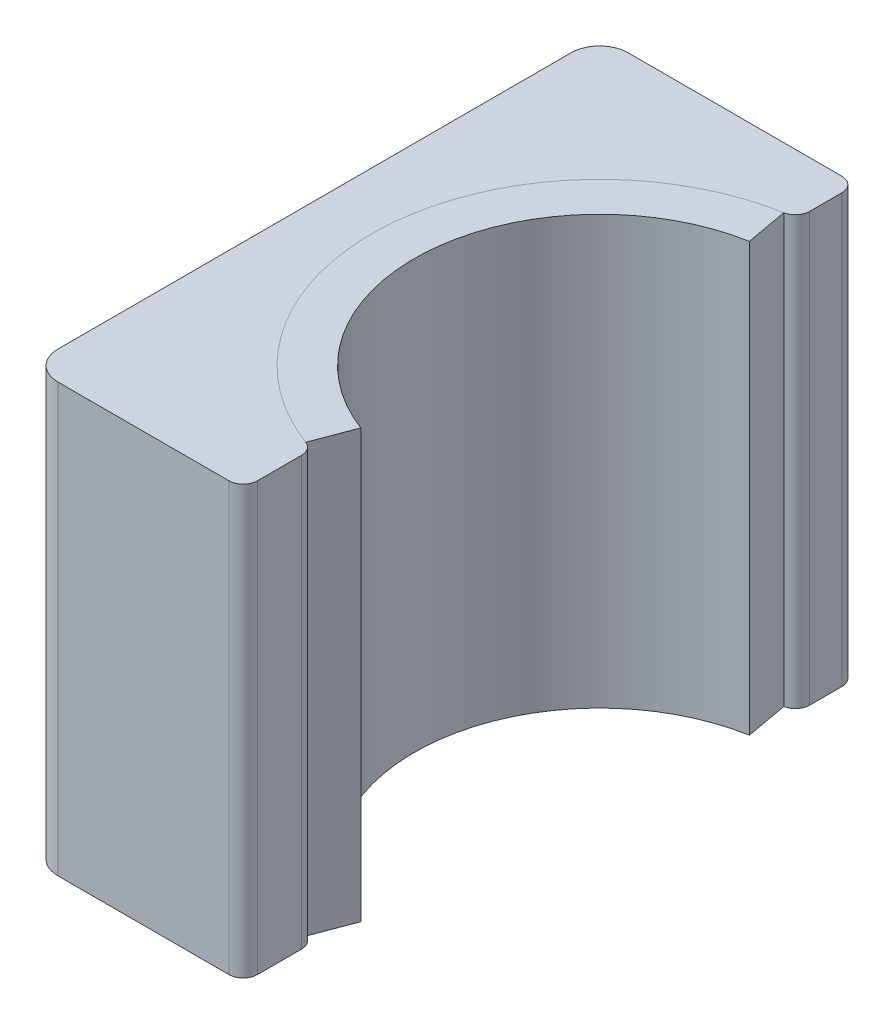
SolidWorks part; units mm, degrees
material "ABS"
ref_plane "正面" through (0, 0, 0) normal (0, 0, 1) x (1, 0, 0)
ref_plane "平面" through (0, 0, 0) normal (0, 1, 0) x (1, 0, 0)
ref_plane "右側面" through (0, 0, 0) normal (1, 0, 0) x (0, 0, -1)
sketch "ｽｹｯﾁ1" plane through (0, 0, 0) normal (0, 1, 0) x (1, 0, 0)
  line L0 (0, 20) -> (0, -20)
  line L1 (0, 0) -> (95.312, 0) construction
  line L2 (0, 20) -> (17, 20)
  line L3 (18, 19) -> (18, 16.7332)
  line L5 (14, -20) -> (0, -20)
  line L6 (15, -15.906) -> (15, -19)
  arc A0 (17.1765, 15.7489) -> (14.3529, -14.9703) centre (20, 0) ccw
  arc A2 (17, 20) -> (18, 19) centre (17, 19) cw
  arc A4 (18, 16.7332) -> (17.1765, 15.7489) centre (17, 16.7332) cw
  arc A5 (15, -19) -> (14, -20) centre (14, -19) cw
  arc A6 (15, -15.906) -> (14.3529, -14.9703) centre (14, -15.906) ccw
  point P19 (18, 20)
  point P24 (18, 15.8745)
  dimension "D1" = 16
  dimension "D5" = 1
  dimension "D7" = 1
  dimension "D8" = 1
  dimension "D2" = 40
  dimension "D3" = 18
  dimension "D4" = 2
  dimension "D6" = 3
extrude "ﾎﾞｽ - 押し出し1" add sketch "ｽｹｯﾁ1" along normal blind 15 and the other way blind 15
sketch "ｽｹｯﾁ2" plane through (18, 0, 0) normal (1, 0, 0) x (0, 0, -1)
  line L0 (-19, 15) -> (19, 15) construction
  line L1 (8, 12.9571) -> (8, -14.7101) construction
  line L2 (9.9, 0) -> (-9.9, 0) construction
  line L5 (20, -15) -> (20, 15) construction
  circle A0 centre (8, 10.5) radius 1.1
  circle A1 centre (8, -10.5) radius 1.1
  point P13 (0, 0)
  point P14 (0, 12.9571)
  point P17 (0, 0)
  dimension "D1" = 2.2
  dimension "D2" = 10.5
  dimension "D3" = 12
extrude "ｶｯﾄ - 押し出し1" cut sketch "ｽｹｯﾁ2" against normal through all
ref_plane "平面1" through (10, 0, 0) normal (-1, 0, 0) x (0, 0, 1)
sketch "ｽｹｯﾁ3" plane through (10, 0, 0) normal (-1, 0, 0) x (0, 0, 1)
  circle A0 centre (-8, 10.5) radius 3
  circle A1 centre (-8, -10.5) radius 3
  circle A2 centre (-8, -10.5) radius 1.1 construction
  circle A3 centre (-8, 10.5) radius 1.1 construction
  dimension "D1" = 6
extrude "ｶｯﾄ - 押し出し2" cut sketch "ｽｹｯﾁ3" along normal blind 8
fillet "ﾌｨﾚｯﾄ1" radius 2 2 edges at (0, 0, 20) (0, 0, -20)
sketch "ｽｹｯﾁ5" plane through (0, 15, 0) normal (0, 1, 0) x (1, 0, 0)
  line L0 (17.1765, 15.7489) -> (17.7059, 12.796)
  line L1 (15.4118, -12.1634) -> (14.3529, -14.9703)
  arc A0 (17.1765, 15.7489) -> (14.3529, -14.9703) centre (20, 0) ccw construction
  arc A1 (17.1765, 15.7489) -> (14.3529, -14.9703) centre (20, 0) ccw
  arc A2 (17.7059, 12.796) -> (15.4118, -12.1634) centre (20, 0) ccw
  point P9 (13.9971, -14.8312)
  dimension "D1" = 26
extrude "ﾎﾞｽ - 押し出し2" add sketch "ｽｹｯﾁ5" against normal up to surface (30 mm away) separate body up to face at (10.0619, -15, -0.2194)
